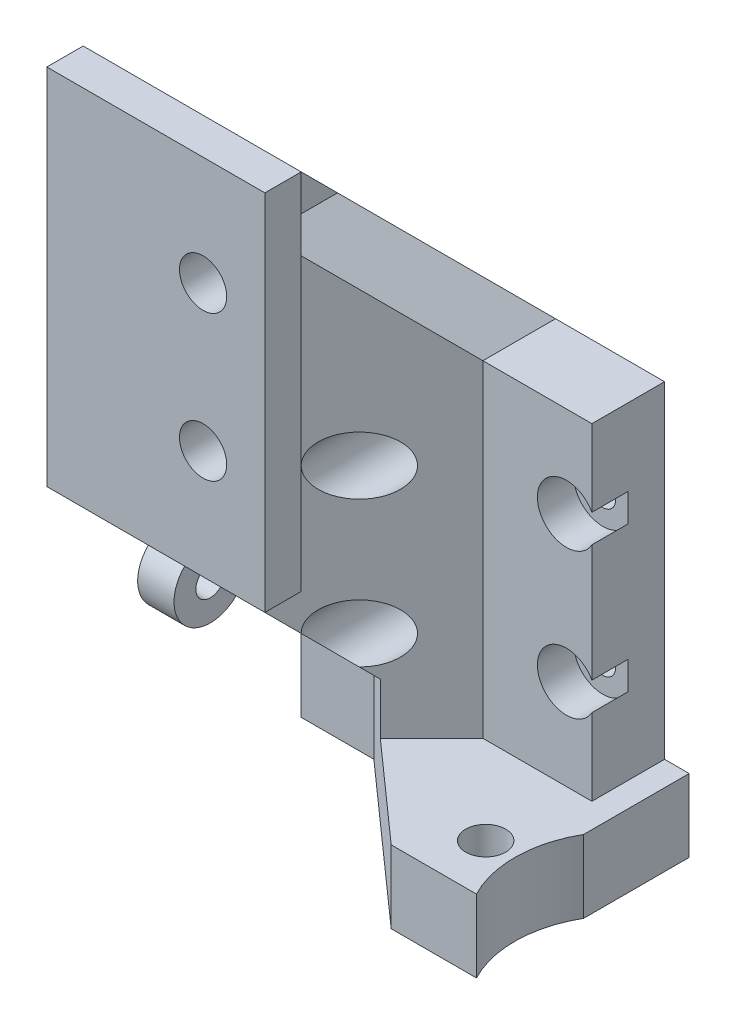
SolidWorks part; units mm, degrees
ref_plane "Plan de face" through (0, 0, 0) normal (0, 0, 1) x (1, 0, 0)
ref_plane "Plan de dessus" through (0, 0, 0) normal (0, 1, 0) x (1, 0, 0)
ref_plane "Plan de droite" through (0, 0, 0) normal (1, 0, 0) x (0, 0, -1)
sketch "Esquisse1" plane through (0, 0, 0) normal (0, 0, 1) x (1, 0, 0)
  line L1 (-40, 45) -> (0, 45)
  line L2 (-40, 45) -> (-40, 0)
  line L3 (-40, 0) -> (0, 0)
  line L4 (0, 45) -> (0, 0)
  circle A0 centre (-3.5, 32.5) radius 1.75
  circle A1 centre (-23.5, 32.5) radius 1.75
  circle A2 centre (-23.5, 12.5) radius 1.75
  circle A3 centre (-3.5, 12.5) radius 1.75
  point P4 (0, 0)
  point P5 (-29.5373, 12.5)
  dimension "D5" = 3.5
  dimension "D1" = 3.5
  dimension "D2" = 40
  dimension "D3" = 45
  dimension "D4" = 20
  dimension "D6" = 12.5
  dimension "D8" = 20
extrude "Boss.-Extru.1" add sketch "Esquisse1" along normal blind 10
sketch "Esquisse2" plane through (0, 0, 10) normal (0, 0, 1) x (1, 0, 0)
  circle A0 centre (-23.5, 32.5) radius 4
  circle A1 centre (-3.5, 32.5) radius 4
  circle A2 centre (-23.5, 12.5) radius 4
  circle A3 centre (-3.5, 12.5) radius 4
  dimension "D1" = 8
extrude "Enlèv. mat.-Extru.2" cut sketch "Esquisse2" against normal blind 5
sketch "Esquisse3" plane through (-40, 0, 0) normal (-1, 0, 0) x (0, 0, 1)
  line L0 (10, 0) -> (45, 35)
  line L1 (45, 35) -> (45, 85)
  line L2 (45, 85) -> (40, 85)
  line L3 (40, 85) -> (0, 45)
  line L4 (10, 45) -> (0, 45) construction
  line L5 (0, 45) -> (0, 0) construction
  line L6 (0, 45) -> (10, 45)
  line L7 (10, 45) -> (10, 0)
  dimension "D1" = 45
  dimension "D2" = 30
  dimension "D3" = 50
extrude "Boss.-Extru.2" add sketch "Esquisse3" against normal blind 10
sketch "Esquisse4" plane through (-30, 0, 0) normal (1, 0, 0) x (0, 0, -1)
  line L0 (-45, 85) -> (-45, 35)
  line L6 (-40, 35) -> (-40, 85)
  line L7 (-40, 85) -> (0, 45) construction
  line L10 (-45, 35) -> (-40, 35)
  line L11 (-45, 85) -> (-40, 85)
  dimension "D1" = 5
extrude "Boss.-Extru.3" add sketch "Esquisse4" along normal blind 20
sketch "Esquisse5" plane through (0, 0, 45) normal (0, 0, 1) x (1, 0, 0)
  line L0 (-18.5, 70) -> (-18.5, 50) construction
  line L1 (-10, 85) -> (-10, 35) construction
  circle A0 centre (-18.5, 70) radius 3.25
  circle A1 centre (-18.5, 50) radius 3.25
  circle A2 centre (-3.5, 12.5) radius 1.75 construction
  circle A3 centre (-3.5, 12.5) radius 1.75 construction
  point P4 (-18.5, 60)
  point P7 (-10, 60)
  point P11 (0, 0)
  dimension "D1" = 6.5
  dimension "D2" = 20
  dimension "D3" = 15
extrude "Enlèv. mat.-Extru.3" cut sketch "Esquisse5" against normal up to next
sketch "Esquisse8" plane through (0, 0, 0) normal (0, -1, 0) x (1, 0, 0)
  line L0 (-30, 10) -> (0, 10) construction
  line L1 (3.3834, 0) -> (-40, 0)
  line L2 (3.3834, 0) -> (3.3834, 29)
  line L3 (3.3834, 29) -> (-8.6166, 29)
  line L5 (-40, 10) -> (-30, 10)
  line L6 (0, 10) -> (0, 0) construction
  line L8 (-40, 0) -> (-40, 10)
  line L10 (-30, 10) -> (-8.6166, 29)
  circle A0 centre (-2.6166, 22) radius 2.75
  point P14 (-2.6166, 29)
  dimension "D1" = 5.5
  dimension "D2" = 12
  dimension "D3" = 7
  dimension "D4" = 2.6166
  dimension "D5" = 12
extrude "Boss.-Extru.8" add sketch "Esquisse8" along normal blind 10
sketch "Esquisse9" plane through (0, -10, 0) normal (0, -1, 0) x (1, 0, 0)
  circle A0 centre (16.3834, 22) radius 15
  circle A1 centre (-2.6166, 22) radius 2.75 construction
  circle A2 centre (-2.6166, 22) radius 2.75 construction
  point P5 (0, 0)
  dimension "D2" = 30
  dimension "D1" = 19
extrude "Enlèv. mat.-Extru.5" cut sketch "Esquisse9" against normal up to next
chamfer "Chanfrein2" distance 15 angle 45 3 edges at (-30, 45, 5) (-30, 22.5, 10) (-30, 60, 40)
sketch "Esquisse6" plane through (0, 0, 40) normal (0, 0, -1) x (-1, 0, 0)
  line L0 (10.5, 70) -> (10.5, 85)
  line L1 (10, 85) -> (15, 85) construction
  line L2 (10.5, 85) -> (26.5, 85)
  line L3 (15, 85) -> (40, 85) construction
  line L4 (26.5, 85) -> (26.5, 70)
  line L5 (10.5, 50) -> (10.5, 35)
  line L6 (10, 35) -> (15, 35) construction
  line L7 (10.5, 35) -> (26.5, 35)
  line L8 (26.5, 35) -> (26.5, 50)
  arc A2 (10.5, 70) -> (26.5, 70) centre (18.5, 70) ccw
  arc A3 (10.5, 50) -> (26.5, 50) centre (18.5, 50) cw
  dimension "D2" = 8
extrude "Enlèv. mat.-Extru.4" cut sketch "Esquisse6" along normal up to next
chamfer "Chanfrein3" distance 3.5 angle 45 1 edges at (-30, 35, 35)
sketch "Esquisse7" plane through (-40, 0, 0) normal (-1, 0, 0) x (0, 0, 1)
  line L0 (10, 0) -> (45, 35) construction
  line L1 (28.9142, 18.9142) -> (31.0355, 21.0355)
  line L2 (26.0858, 16.0858) -> (23.9645, 13.9645)
  arc A0 (23.9645, 13.9645) -> (31.0355, 21.0355) centre (27.5, 17.5) ccw
  arc A1 (26.0858, 16.0858) -> (28.9142, 18.9142) centre (27.5, 17.5) ccw
  dimension "D1" = 2
  dimension "D2" = 5
extrude "Boss.-Extru.4" add sketch "Esquisse7" against normal blind 5
